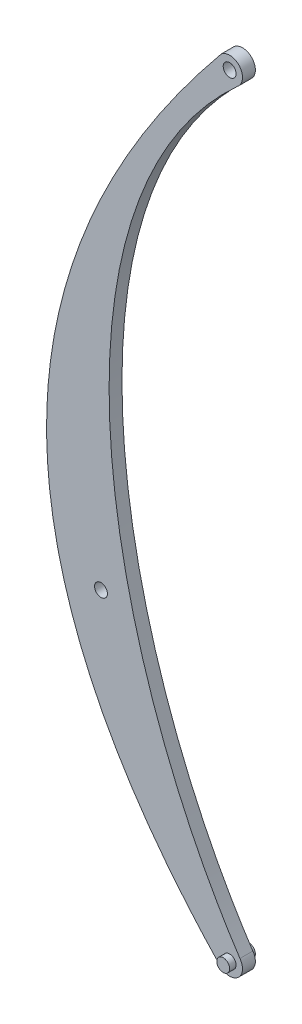
SolidWorks part; units mm, degrees
ref_plane "Front Plane" through (0, 0, 0) normal (0, 0, 1) x (1, 0, 0)
ref_plane "Top Plane" through (0, 0, 0) normal (0, 1, 0) x (1, 0, 0)
ref_plane "Right Plane" through (0, 0, 0) normal (1, 0, 0) x (0, 0, -1)
sketch "Sketch1" plane through (0, 0, 0) normal (0, 0, 1) x (1, 0, 0)
  line L0 (0, 0) -> (0, 600) construction
  line L1 (0, 0) -> (-100, 0) construction
  line L2 (-100, 0) -> (-100, 200) construction
  circle A0 centre (0, 0) radius 5
  circle A1 centre (0, 600) radius 5
  circle A2 centre (0, 0) radius 10
  circle A3 centre (0, 600) radius 10
  circle A4 centre (-100, 200) radius 5
  spline S0 degree 3 poles (6.0546, 592.0413) (-154.8619, 445.1299) (-96.2969, 163.3062) (8.0284, 5.9619) knots 0 0 0 0 1 1 1 1
  spline S1 degree 2 poles (-6.4254, 607.6625) (-277.8432, 277.3044) (-7.075, -7.0672) knots 0 0 0 1 1 1
  dimension "D1" = 10
  dimension "D2" = 10
  dimension "D7" = 10
  dimension "D4" = 600
  dimension "D5" = 200
  dimension "D6" = 100
  dimension "D3" = 5
extrude "Boss-Extrude1" add sketch "Sketch1" along normal blind 5 contours A2 L0 S0 A3 S1 | A3 S1 A1 | A0 A2 S0 | L0 A2 S0 region at (3.7161, -8.9785, 0) region at (-10.3424, 12.5948, 0) region at (-6.3303, 592.6277, 0)
extrude "Boss-Extrude2" add sketch "Sketch1<3>" along normal blind 10 contours A0 region at (0, 0, 0)
sketch "Sketch1<3>" plane through (0, 0, 0) normal (0, 0, 1) x (1, 0, 0) same geometry as "Sketch1"
mirror "Mirror1" about plane through (0, 0, 0) normal (0, 0, 1) of "Boss-Extrude2", "Boss-Extrude1"
